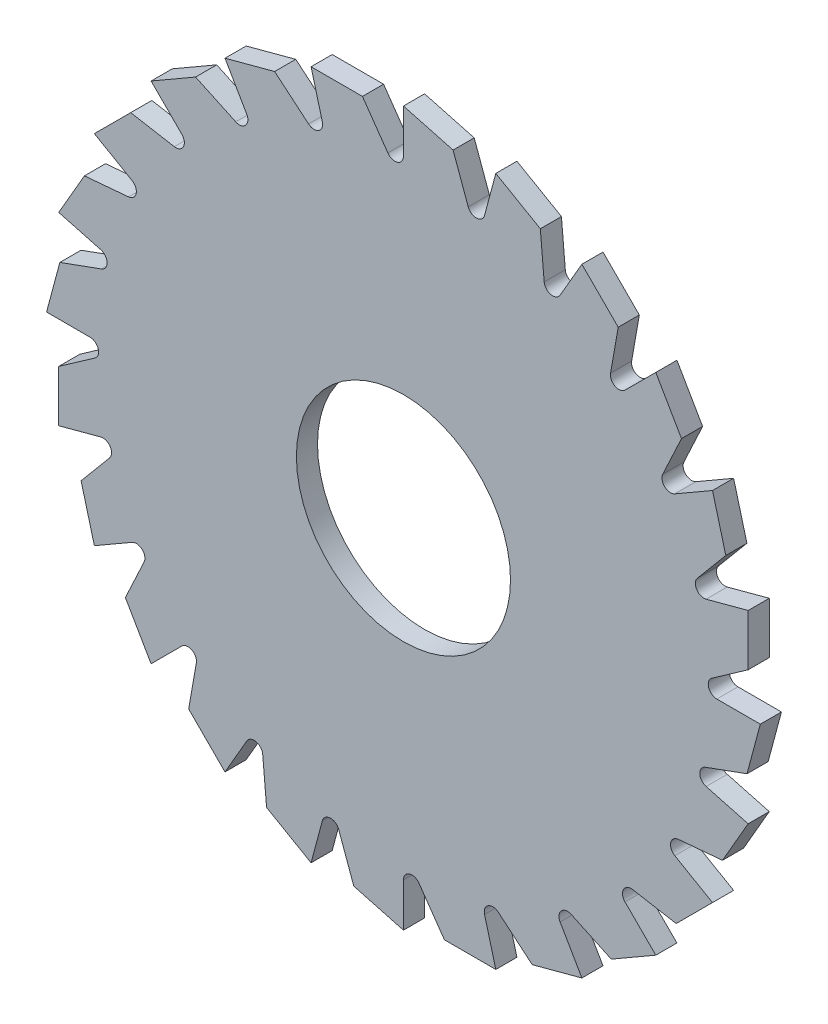
SolidWorks part; units mm, degrees
ref_plane "Front Plane" through (0, 0, 0) normal (0, 0, 1) x (1, 0, 0)
ref_plane "Top Plane" through (0, 0, 0) normal (0, 1, 0) x (1, 0, 0)
ref_plane "Right Plane" through (0, 0, 0) normal (1, 0, 0) x (0, 0, -1)
sketch "Sketch1" plane through (0, 0, 0) normal (0, 0, 1) x (1, 0, 0)
  line L0 (0, 31.75) -> (4.4162, 30.5667)
  line L1 (4.4162, 30.5667) -> (5.7634, 26.8652)
  line L2 (7.2155, 26.9286) -> (8.2175, 30.6681)
  line L3 (0, 31.75) -> (0, 0) construction
  line L4 (0, 0) -> (8.2175, 30.6681) construction
  line L5 (0, 31.75) -> (12.0811, 31.75) construction
  line L6 (6.3024, 26.3847) -> (0, 0) construction
  line L7 (6.3024, 26.3847) -> (4.0698, 26.918) construction
  line L8 (13.9393, 24.1436) -> (15.875, 27.4963)
  line L9 (12.177, 28.3821) -> (12.5203, 24.4581)
  line L10 (8.2175, 30.6681) -> (12.177, 28.3821)
  line L11 (19.7131, 19.7131) -> (22.4506, 22.4506)
  line L12 (19.1079, 24.2634) -> (18.4239, 20.3843)
  line L13 (15.875, 27.4963) -> (19.1079, 24.2634)
  line L14 (24.1436, 13.9393) -> (27.4963, 15.875)
  line L15 (24.7366, 18.4912) -> (23.072, 14.9212)
  line L16 (22.4506, 22.4506) -> (24.7366, 18.4912)
  line L17 (26.9286, 7.2155) -> (30.6681, 8.2175)
  line L18 (28.6796, 11.4588) -> (26.1477, 8.4413)
  line L19 (27.4963, 15.875) -> (28.6796, 11.4588)
  line L20 (27.8786, 0) -> (31.75, 0)
  line L21 (30.6681, 3.6455) -> (27.4415, 1.3862)
  line L22 (30.6681, 8.2175) -> (30.6681, 3.6455)
  line L23 (26.9286, -7.2155) -> (30.6681, -8.2175)
  line L24 (30.5667, -4.4162) -> (26.8652, -5.7634)
  line L25 (31.75, 0) -> (30.5667, -4.4162)
  line L26 (24.1436, -13.9393) -> (27.4963, -15.875)
  line L27 (28.3821, -12.177) -> (24.4581, -12.5203)
  line L28 (30.6681, -8.2175) -> (28.3821, -12.177)
  line L29 (19.7131, -19.7131) -> (22.4506, -22.4506)
  line L30 (24.2634, -19.1079) -> (20.3843, -18.4239)
  line L31 (27.4963, -15.875) -> (24.2634, -19.1079)
  line L32 (13.9393, -24.1436) -> (15.875, -27.4963)
  line L33 (18.4912, -24.7366) -> (14.9212, -23.072)
  line L34 (22.4506, -22.4506) -> (18.4912, -24.7366)
  line L35 (7.2155, -26.9286) -> (8.2175, -30.6681)
  line L36 (11.4588, -28.6796) -> (8.4413, -26.1477)
  line L37 (15.875, -27.4963) -> (11.4588, -28.6796)
  line L38 (0, -27.8786) -> (0, -31.75)
  line L39 (3.6455, -30.6681) -> (1.3862, -27.4415)
  line L40 (8.2175, -30.6681) -> (3.6455, -30.6681)
  line L41 (-7.2155, -26.9286) -> (-8.2175, -30.6681)
  line L42 (-4.4162, -30.5667) -> (-5.7634, -26.8652)
  line L43 (0, -31.75) -> (-4.4162, -30.5667)
  line L44 (-13.9393, -24.1436) -> (-15.875, -27.4963)
  line L45 (-12.177, -28.3821) -> (-12.5203, -24.4581)
  line L46 (-8.2175, -30.6681) -> (-12.177, -28.3821)
  line L47 (-19.7131, -19.7131) -> (-22.4506, -22.4506)
  line L48 (-19.1079, -24.2634) -> (-18.4239, -20.3843)
  line L49 (-15.875, -27.4963) -> (-19.1079, -24.2634)
  line L50 (-24.1436, -13.9393) -> (-27.4963, -15.875)
  line L51 (-24.7366, -18.4912) -> (-23.072, -14.9212)
  line L52 (-22.4506, -22.4506) -> (-24.7366, -18.4912)
  line L53 (-26.9286, -7.2155) -> (-30.6681, -8.2175)
  line L54 (-28.6796, -11.4588) -> (-26.1477, -8.4413)
  line L55 (-27.4963, -15.875) -> (-28.6796, -11.4588)
  line L56 (-27.8786, 0) -> (-31.75, 0)
  line L57 (-30.6681, -3.6455) -> (-27.4415, -1.3862)
  line L58 (-30.6681, -8.2175) -> (-30.6681, -3.6455)
  line L59 (-26.9286, 7.2155) -> (-30.6681, 8.2175)
  line L60 (-30.5667, 4.4162) -> (-26.8652, 5.7634)
  line L61 (-31.75, 0) -> (-30.5667, 4.4162)
  line L62 (-24.1436, 13.9393) -> (-27.4963, 15.875)
  line L63 (-28.3821, 12.177) -> (-24.4581, 12.5203)
  line L64 (-30.6681, 8.2175) -> (-28.3821, 12.177)
  line L65 (-19.7131, 19.7131) -> (-22.4506, 22.4506)
  line L66 (-24.2634, 19.1079) -> (-20.3843, 18.4239)
  line L67 (-27.4963, 15.875) -> (-24.2634, 19.1079)
  line L68 (-13.9393, 24.1436) -> (-15.875, 27.4963)
  line L69 (-18.4912, 24.7366) -> (-14.9212, 23.072)
  line L70 (-22.4506, 22.4506) -> (-18.4912, 24.7366)
  line L71 (-7.2155, 26.9286) -> (-8.2175, 30.6681)
  line L72 (-11.4588, 28.6796) -> (-8.4413, 26.1477)
  line L73 (-15.875, 27.4963) -> (-11.4588, 28.6796)
  line L74 (0, 27.8786) -> (0, 31.75)
  line L75 (-3.6455, 30.6681) -> (-1.3862, 27.4415)
  line L76 (-8.2175, 30.6681) -> (-3.6455, 30.6681)
  circle A0 centre (0, 0) radius 31.75 construction
  circle A1 centre (0, 0) radius 9.525
  circle A2 centre (0, 0) radius 27.127 construction
  arc A3 (5.7634, 26.8652) -> (7.2155, 26.9286) centre (6.4795, 27.1259) ccw
  arc A4 (12.5203, 24.4581) -> (13.9393, 24.1436) centre (13.2794, 24.5246) ccw
  arc A5 (18.4239, 20.3843) -> (19.7131, 19.7131) centre (19.1743, 20.2519) ccw
  arc A6 (23.072, 14.9212) -> (24.1436, 13.9393) centre (23.7626, 14.5992) ccw
  arc A7 (26.1477, 8.4413) -> (26.9286, 7.2155) centre (26.7314, 7.9515) ccw
  arc A8 (27.4415, 1.3862) -> (27.8786, 0) centre (27.8786, 0.762) ccw
  arc A9 (26.8652, -5.7634) -> (26.9286, -7.2155) centre (27.1259, -6.4795) ccw
  arc A10 (24.4581, -12.5203) -> (24.1436, -13.9393) centre (24.5246, -13.2794) ccw
  arc A11 (20.3843, -18.4239) -> (19.7131, -19.7131) centre (20.2519, -19.1743) ccw
  arc A12 (14.9212, -23.072) -> (13.9393, -24.1436) centre (14.5992, -23.7626) ccw
  arc A13 (8.4413, -26.1477) -> (7.2155, -26.9286) centre (7.9515, -26.7314) ccw
  arc A14 (1.3862, -27.4415) -> (0, -27.8786) centre (0.762, -27.8786) ccw
  arc A15 (-5.7634, -26.8652) -> (-7.2155, -26.9286) centre (-6.4795, -27.1259) ccw
  arc A16 (-12.5203, -24.4581) -> (-13.9393, -24.1436) centre (-13.2794, -24.5246) ccw
  arc A17 (-18.4239, -20.3843) -> (-19.7131, -19.7131) centre (-19.1743, -20.2519) ccw
  arc A18 (-23.072, -14.9212) -> (-24.1436, -13.9393) centre (-23.7626, -14.5992) ccw
  arc A19 (-26.1477, -8.4413) -> (-26.9286, -7.2155) centre (-26.7314, -7.9515) ccw
  arc A20 (-27.4415, -1.3862) -> (-27.8786, 0) centre (-27.8786, -0.762) ccw
  arc A21 (-26.8652, 5.7634) -> (-26.9286, 7.2155) centre (-27.1259, 6.4795) ccw
  arc A22 (-24.4581, 12.5203) -> (-24.1436, 13.9393) centre (-24.5246, 13.2794) ccw
  arc A23 (-20.3843, 18.4239) -> (-19.7131, 19.7131) centre (-20.2519, 19.1743) ccw
  arc A24 (-14.9212, 23.072) -> (-13.9393, 24.1436) centre (-14.5992, 23.7626) ccw
  arc A25 (-8.4413, 26.1477) -> (-7.2155, 26.9286) centre (-7.9515, 26.7314) ccw
  arc A26 (-1.3862, 27.4415) -> (0, 27.8786) centre (-0.762, 27.8786) ccw
  dimension "D1" = 63.5
  dimension "D2" = 19.05
  dimension "D3" = 125
  dimension "D7" = 0.762
  dimension "D4" = 15
  dimension "D5" = 15
  dimension "D6" = 4.572
  dimension "D8" = 24
extrude "Boss-Extrude1" add sketch "Sketch1" along normal blind 1.8796 contours A26 L75 L76 L71 A25 L72 L73 L68 A24 L69 L70 L65 A23 L66 L67 L62 A22 L63 L64 L59 A21 L60 L61 L56 A20 L57 L58 L53 A19 L54 L55 L50 A18 L51 L52 L47 A17 L48 L49 L44 A16 L45 L46 L41 A15 L42 L43 L38 A14 L39 L40 region at (1.9757, 30.2909, 0)
ref_plane "Plane1" through (0, 0, 0.9398) normal (0, 0, 1) x (1, 0, 0)
sketch "Sketch2" plane through (0, 0, 0) normal (0, 0, 1) x (1, 0, 0)
  line L0 (31.75, -31.75) -> (31.75, 31.75)
  line L1 (400.05, -31.75) -> (-31.75, -31.75)
  line L2 (400.05, -31.75) -> (400.05, 400.05)
  line L3 (400.05, 400.05) -> (-31.75, 400.05)
  line L4 (-31.75, -31.75) -> (-31.75, 400.05)
  line L5 (184.15, 400.05) -> (184.15, -31.75) construction
  line L6 (400.05, 184.15) -> (-31.75, 184.15) construction
  line L7 (-31.75, -31.75) -> (31.75, -31.75)
  line L8 (-31.75, -31.75) -> (-31.75, 31.75)
  line L9 (-31.75, 31.75) -> (31.75, 31.75)
  line L10 (31.75, -31.75) -> (31.75, 31.75)
  line L11 (0, 31.75) -> (0, -31.75) construction
  line L12 (-31.75, 0) -> (31.75, 0) construction
  line L13 (31.75, -31.75) -> (95.25, -31.75)
  line L14 (95.25, -31.75) -> (95.25, 31.75)
  line L15 (31.75, 31.75) -> (95.25, 31.75)
  line L16 (95.25, -31.75) -> (95.25, 31.75)
  line L17 (95.25, -31.75) -> (158.75, -31.75)
  line L18 (158.75, -31.75) -> (158.75, 31.75)
  line L19 (95.25, 31.75) -> (158.75, 31.75)
  line L20 (158.75, -31.75) -> (158.75, 31.75)
  line L21 (158.75, -31.75) -> (222.25, -31.75)
  line L22 (222.25, -31.75) -> (222.25, 31.75)
  line L23 (158.75, 31.75) -> (222.25, 31.75)
  line L24 (222.25, -31.75) -> (222.25, 31.75)
  line L25 (222.25, -31.75) -> (285.75, -31.75)
  line L26 (285.75, -31.75) -> (285.75, 31.75)
  line L27 (222.25, 31.75) -> (285.75, 31.75)
  line L28 (285.75, -31.75) -> (285.75, 31.75)
  line L29 (285.75, -31.75) -> (349.25, -31.75)
  line L30 (349.25, -31.75) -> (349.25, 31.75)
  line L31 (285.75, 31.75) -> (349.25, 31.75)
  line L32 (31.75, 31.75) -> (31.75, 95.25)
  line L33 (31.75, 31.75) -> (95.25, 31.75)
  line L34 (95.25, 31.75) -> (95.25, 95.25)
  line L35 (31.75, 95.25) -> (95.25, 95.25)
  line L36 (95.25, 31.75) -> (95.25, 95.25)
  line L37 (95.25, 31.75) -> (158.75, 31.75)
  line L38 (158.75, 31.75) -> (158.75, 95.25)
  line L39 (95.25, 95.25) -> (158.75, 95.25)
  line L40 (158.75, 31.75) -> (158.75, 95.25)
  line L41 (158.75, 31.75) -> (222.25, 31.75)
  line L42 (222.25, 31.75) -> (222.25, 95.25)
  line L43 (158.75, 95.25) -> (222.25, 95.25)
  line L44 (222.25, 31.75) -> (222.25, 95.25)
  line L45 (222.25, 31.75) -> (285.75, 31.75)
  line L46 (285.75, 31.75) -> (285.75, 95.25)
  line L47 (222.25, 95.25) -> (285.75, 95.25)
  line L48 (285.75, 31.75) -> (285.75, 95.25)
  line L49 (285.75, 31.75) -> (349.25, 31.75)
  line L50 (349.25, 31.75) -> (349.25, 95.25)
  line L51 (285.75, 95.25) -> (349.25, 95.25)
  line L52 (31.75, 95.25) -> (31.75, 158.75)
  line L53 (31.75, 95.25) -> (95.25, 95.25)
  line L54 (95.25, 95.25) -> (95.25, 158.75)
  line L55 (31.75, 158.75) -> (95.25, 158.75)
  line L56 (95.25, 95.25) -> (95.25, 158.75)
  line L57 (95.25, 95.25) -> (158.75, 95.25)
  line L58 (158.75, 95.25) -> (158.75, 158.75)
  line L59 (95.25, 158.75) -> (158.75, 158.75)
  line L60 (158.75, 95.25) -> (158.75, 158.75)
  line L61 (158.75, 95.25) -> (222.25, 95.25)
  line L62 (222.25, 95.25) -> (222.25, 158.75)
  line L63 (158.75, 158.75) -> (222.25, 158.75)
  line L64 (222.25, 95.25) -> (222.25, 158.75)
  line L65 (222.25, 95.25) -> (285.75, 95.25)
  line L66 (285.75, 95.25) -> (285.75, 158.75)
  line L67 (222.25, 158.75) -> (285.75, 158.75)
  line L68 (285.75, 95.25) -> (285.75, 158.75)
  line L69 (285.75, 95.25) -> (349.25, 95.25)
  line L70 (349.25, 95.25) -> (349.25, 158.75)
  line L71 (285.75, 158.75) -> (349.25, 158.75)
  line L72 (31.75, 158.75) -> (31.75, 222.25)
  line L73 (31.75, 158.75) -> (95.25, 158.75)
  line L74 (95.25, 158.75) -> (95.25, 222.25)
  line L75 (31.75, 222.25) -> (95.25, 222.25)
  line L76 (95.25, 158.75) -> (95.25, 222.25)
  line L77 (95.25, 158.75) -> (158.75, 158.75)
  line L78 (158.75, 158.75) -> (158.75, 222.25)
  line L79 (95.25, 222.25) -> (158.75, 222.25)
  line L80 (158.75, 158.75) -> (158.75, 222.25)
  line L81 (158.75, 158.75) -> (222.25, 158.75)
  line L82 (222.25, 158.75) -> (222.25, 222.25)
  line L83 (158.75, 222.25) -> (222.25, 222.25)
  line L84 (222.25, 158.75) -> (222.25, 222.25)
  line L85 (222.25, 158.75) -> (285.75, 158.75)
  line L86 (285.75, 158.75) -> (285.75, 222.25)
  line L87 (222.25, 222.25) -> (285.75, 222.25)
  line L88 (285.75, 158.75) -> (285.75, 222.25)
  line L89 (285.75, 158.75) -> (349.25, 158.75)
  line L90 (349.25, 158.75) -> (349.25, 222.25)
  line L91 (285.75, 222.25) -> (349.25, 222.25)
  line L92 (31.75, 222.25) -> (31.75, 285.75)
  line L93 (31.75, 222.25) -> (95.25, 222.25)
  line L94 (95.25, 222.25) -> (95.25, 285.75)
  line L95 (31.75, 285.75) -> (95.25, 285.75)
  line L96 (95.25, 222.25) -> (95.25, 285.75)
  line L97 (95.25, 222.25) -> (158.75, 222.25)
  line L98 (158.75, 222.25) -> (158.75, 285.75)
  line L99 (95.25, 285.75) -> (158.75, 285.75)
  line L100 (158.75, 222.25) -> (158.75, 285.75)
  line L101 (158.75, 222.25) -> (222.25, 222.25)
  line L102 (222.25, 222.25) -> (222.25, 285.75)
  line L103 (158.75, 285.75) -> (222.25, 285.75)
  line L104 (222.25, 222.25) -> (222.25, 285.75)
  line L105 (222.25, 222.25) -> (285.75, 222.25)
  line L106 (285.75, 222.25) -> (285.75, 285.75)
  line L107 (222.25, 285.75) -> (285.75, 285.75)
  line L108 (285.75, 222.25) -> (285.75, 285.75)
  line L109 (285.75, 222.25) -> (349.25, 222.25)
  line L110 (349.25, 222.25) -> (349.25, 285.75)
  line L111 (285.75, 285.75) -> (349.25, 285.75)
  line L112 (31.75, 285.75) -> (31.75, 349.25)
  line L113 (31.75, 285.75) -> (95.25, 285.75)
  line L114 (95.25, 285.75) -> (95.25, 349.25)
  line L115 (31.75, 349.25) -> (95.25, 349.25)
  line L116 (95.25, 285.75) -> (95.25, 349.25)
  line L117 (95.25, 285.75) -> (158.75, 285.75)
  line L118 (158.75, 285.75) -> (158.75, 349.25)
  line L119 (95.25, 349.25) -> (158.75, 349.25)
  line L120 (158.75, 285.75) -> (158.75, 349.25)
  line L121 (158.75, 285.75) -> (222.25, 285.75)
  line L122 (222.25, 285.75) -> (222.25, 349.25)
  line L123 (158.75, 349.25) -> (222.25, 349.25)
  line L124 (222.25, 285.75) -> (222.25, 349.25)
  line L125 (222.25, 285.75) -> (285.75, 285.75)
  line L126 (285.75, 285.75) -> (285.75, 349.25)
  line L127 (222.25, 349.25) -> (285.75, 349.25)
  line L128 (285.75, 285.75) -> (285.75, 349.25)
  line L129 (285.75, 285.75) -> (349.25, 285.75)
  line L130 (349.25, 285.75) -> (349.25, 349.25)
  line L131 (285.75, 349.25) -> (349.25, 349.25)
  line L132 (-31.75, 31.75) -> (-31.75, 95.25)
  line L133 (-31.75, 31.75) -> (31.75, 31.75)
  line L134 (31.75, 31.75) -> (31.75, 95.25)
  line L135 (-31.75, 95.25) -> (31.75, 95.25)
  line L136 (-31.75, 95.25) -> (-31.75, 158.75)
  line L137 (-31.75, 95.25) -> (31.75, 95.25)
  line L138 (31.75, 95.25) -> (31.75, 158.75)
  line L139 (-31.75, 158.75) -> (31.75, 158.75)
  line L140 (-31.75, 158.75) -> (-31.75, 222.25)
  line L141 (-31.75, 158.75) -> (31.75, 158.75)
  line L142 (31.75, 158.75) -> (31.75, 222.25)
  line L143 (-31.75, 222.25) -> (31.75, 222.25)
  line L144 (-31.75, 222.25) -> (-31.75, 285.75)
  line L145 (-31.75, 222.25) -> (31.75, 222.25)
  line L146 (31.75, 222.25) -> (31.75, 285.75)
  line L147 (-31.75, 285.75) -> (31.75, 285.75)
  line L148 (-31.75, 285.75) -> (-31.75, 349.25)
  line L149 (-31.75, 285.75) -> (31.75, 285.75)
  line L150 (31.75, 285.75) -> (31.75, 349.25)
  line L151 (-31.75, 349.25) -> (31.75, 349.25)
  line L152 (-31.75, -31.75) -> (31.75, -31.75) construction
  line L153 (-31.75, -31.75) -> (-31.75, 31.75) construction
  line L155 (-31.75, 400.05) -> (57.15, 400.05)
  line L156 (-31.75, 400.05) -> (-31.75, 349.25)
  line L157 (-31.75, 349.25) -> (57.15, 349.25)
  line L158 (57.15, 400.05) -> (57.15, 349.25)
  line L159 (57.15, 400.05) -> (146.05, 400.05)
  line L160 (57.15, 400.05) -> (57.15, 349.25)
  line L161 (57.15, 349.25) -> (146.05, 349.25)
  line L162 (146.05, 400.05) -> (146.05, 349.25)
  line L163 (146.05, 400.05) -> (234.95, 400.05)
  line L164 (146.05, 400.05) -> (146.05, 349.25)
  line L165 (146.05, 349.25) -> (234.95, 349.25)
  line L166 (234.95, 400.05) -> (234.95, 349.25)
  line L167 (234.95, 400.05) -> (323.85, 400.05)
  line L168 (234.95, 400.05) -> (234.95, 349.25)
  line L169 (234.95, 349.25) -> (323.85, 349.25)
  line L170 (323.85, 400.05) -> (323.85, 349.25)
  point P0 (184.15, 184.15)
  point P4 (0, 0)
  dimension "D1" = 431.8
  dimension "D2" = 431.8
  dimension "D3" = 63.5
  dimension "D4" = 6
  dimension "D6" = 63.5
  dimension "D7" = 63.5
  dimension "D8" = 88.9
  dimension "D9" = 88.9
  dimension "D10" = 88.9
  dimension "D11" = 88.9
  dimension "D5" = 6
